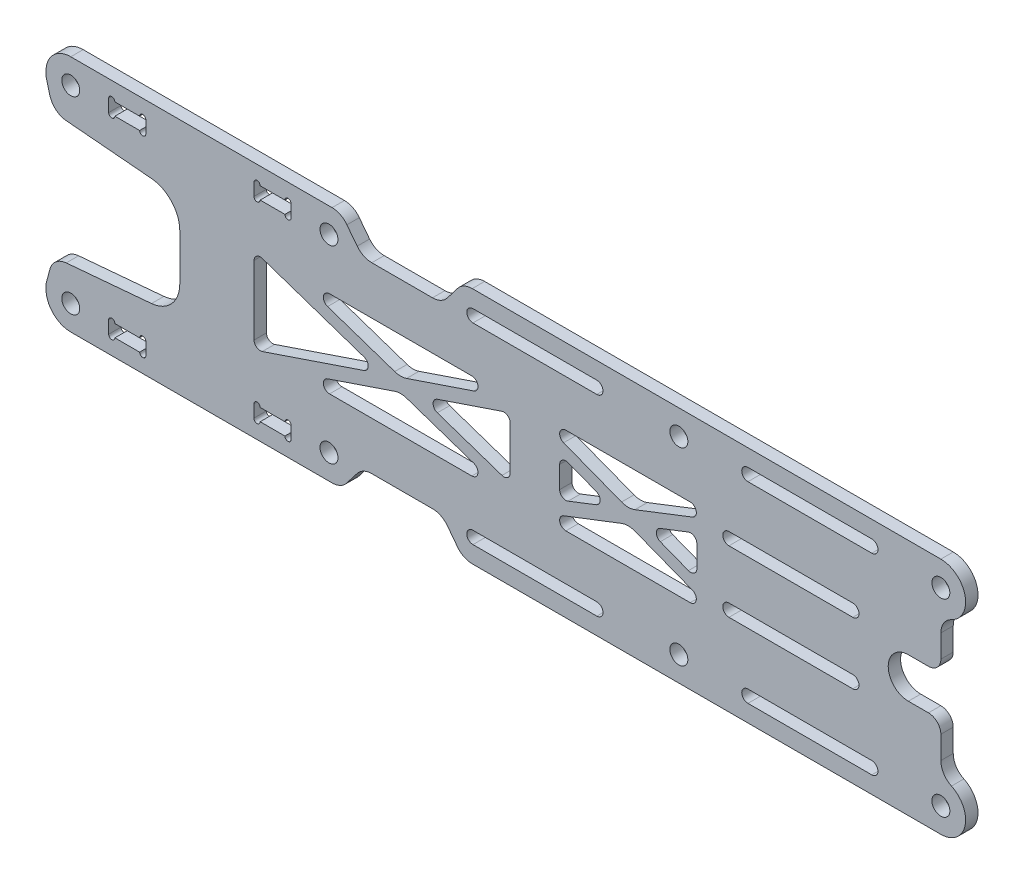
SolidWorks part; units mm, degrees
material "Thornel Mat VMA"
ref_plane "Front Plane" through (0, 0, 0) normal (0, 0, 1) x (1, 0, 0)
ref_plane "Top Plane" through (0, 0, 0) normal (0, 1, 0) x (1, 0, 0)
ref_plane "Right Plane" through (0, 0, 0) normal (1, 0, 0) x (0, 0, -1)
sketch "Sketch1" plane through (0, 0, 0) normal (0, 0, 1) x (1, 0, 0)
  line L0 (38.4052, -16.5) -> (58.4052, -16.5)
  line L1 (58.4052, -14.5) -> (38.4052, -14.5)
  line L2 (-6, -16.5) -> (14, -16.5)
  line L3 (14, -14.5) -> (-6, -14.5)
  line L4 (-59.8318, -16.5) -> (-63.8318, -16.5)
  line L5 (-64.8318, -16.5) -> (-64.8318, -14.5)
  line L6 (-63.8318, -14.5) -> (-59.8318, -14.5)
  line L7 (-58.8318, -14.5) -> (-58.8318, -16.5)
  line L8 (-6, 16.5) -> (14, 16.5)
  line L9 (14, 14.5) -> (-6, 14.5)
  line L10 (-59.8318, 16.5) -> (-63.8318, 16.5)
  line L11 (-64.8318, 16.5) -> (-64.8318, 14.5)
  line L12 (-63.8318, 14.5) -> (-59.8318, 14.5)
  line L13 (-58.8318, 14.5) -> (-58.8318, 16.5)
  line L14 (-36.3681, -16.5) -> (-40.3681, -16.5)
  line L15 (-41.3681, -16.5) -> (-41.3681, -14.5)
  line L16 (-40.3681, -14.5) -> (-36.3681, -14.5)
  line L17 (-35.3681, -14.5) -> (-35.3681, -16.5)
  line L18 (-36.3681, 16.5) -> (-40.3681, 16.5)
  line L19 (-41.3681, 16.5) -> (-41.3681, 14.5)
  line L20 (-40.3681, 14.5) -> (-36.3681, 14.5)
  line L21 (-35.3681, 14.5) -> (-35.3681, 16.5)
  line L22 (38.4052, 16.5) -> (58.4052, 16.5)
  line L23 (58.4052, 14.5) -> (38.4052, 14.5)
  line L24 (-70.9498, 19.25) -> (-28.7512, 19.25)
  line L25 (-22.3376, 14.75) -> (-12.5266, 14.75)
  line L26 (-6.113, 19.25) -> (69.5603, 19.25)
  line L27 (69.5603, 8.9254) -> (69.5603, 5.25)
  line L28 (67.5603, 3.25) -> (64.3092, 3.25)
  line L29 (64.3092, -3.25) -> (67.5603, -3.25)
  line L30 (69.5603, -5.25) -> (69.5603, -8.9254)
  line L31 (69.5603, -19.25) -> (-6.113, -19.25)
  line L32 (-28.7512, -19.25) -> (-70.9498, -19.25)
  line L33 (-74.9498, -15.25) -> (-74.9498, -14.5)
  line L34 (-74.9498, -14.5) -> (-74.3225, -12.1587)
  line L35 (-71.6862, -9.9466) -> (-57.9122, -8.7415)
  line L36 (-53.348, -3.7605) -> (-53.348, 3.7605)
  line L37 (-57.9122, 8.7415) -> (-71.6862, 9.9466)
  line L38 (-74.3225, 12.1587) -> (-74.9498, 14.5)
  line L39 (-74.9498, 14.5) -> (-74.9498, 15.25)
  line L40 (-41.348, 5.5656) -> (-41.348, -5.5656)
  line L41 (-40.0273, -6.5128) -> (-23.5895, -0.9472)
  line L42 (-23.5895, 0.9472) -> (-40.0273, 6.5128)
  line L43 (-29.1583, -7) -> (-6.1897, -7)
  line L44 (-5.869, -5.0528) -> (-16.7119, -1.3815)
  line L45 (-18.6361, -1.3815) -> (-29.479, -5.0528)
  line L46 (-29.479, 5.0528) -> (-18.6361, 1.3815)
  line L47 (-16.7119, 1.3815) -> (-5.869, 5.0528)
  line L48 (-6.1897, 7) -> (-29.1583, 7)
  line L49 (-11.7584, -0.9472) -> (-1.3207, -4.4813)
  line L50 (0, -3.5341) -> (0, 3.5341)
  line L51 (-1.3207, 4.4813) -> (-11.7584, 0.9472)
  line L52 (8.6403, 5.0669) -> (18.0001, 1.4587)
  line L53 (20.1668, 1.462) -> (29.4369, 5.068)
  line L54 (29.0744, 7) -> (9, 7)
  line L55 (-22.3376, -14.75) -> (-12.5266, -14.75)
  line L56 (8.6403, -5.1469) -> (18.0001, -1.5386)
  line L57 (20.1668, -1.5419) -> (29.4369, -5.148)
  line L58 (29.0744, -7.0799) -> (9, -7.0799)
  line L59 (8, 1.7131) -> (8, -1.8089)
  line L60 (9.3625, -2.7409) -> (13.9099, -0.9719)
  line L61 (13.9071, 0.8931) -> (9.3597, 2.6461)
  line L62 (30.1584, 1.7131) -> (30.1584, -1.8089)
  line L63 (28.7959, -2.7409) -> (24.2485, -0.9719)
  line L64 (24.2513, 0.8931) -> (28.7987, 2.6461)
  line L65 (35.3391, 6) -> (55.3391, 6)
  line L66 (55.3391, 4) -> (35.3391, 4)
  line L67 (35.3391, -6) -> (55.3391, -6)
  line L68 (55.3391, -4) -> (35.3391, -4)
  arc A6 (-26.351, 18.0497) -> (-28.7512, 19.25) centre (-28.7512, 16.25) ccw
  arc A7 (-26.351, 18.0497) -> (-24.6948, 15.8942) centre (65.9638, 87.2689) ccw
  arc A8 (-24.6948, 15.8942) -> (-22.3376, 14.75) centre (-22.3376, 17.75) ccw
  arc A9 (71.2746, 11.636) -> (69.5603, 19.25) centre (69.5603, 15.25) ccw
  arc A10 (71.2746, 11.636) -> (69.5603, 8.9254) centre (72.5603, 8.9254) ccw
  arc A11 (67.5603, 3.25) -> (69.5603, 5.25) centre (67.5603, 5.25) ccw
  arc A12 (64.3092, 3.25) -> (64.3092, -3.25) centre (64.3092, 0) ccw
  arc A13 (69.5603, -5.25) -> (67.5603, -3.25) centre (67.5603, -5.25) ccw
  arc A14 (69.5603, -8.9254) -> (71.2746, -11.636) centre (72.5603, -8.9254) ccw
  arc A15 (69.5603, -19.25) -> (71.2746, -11.636) centre (69.5603, -15.25) ccw
  arc A16 (-74.9498, -15.25) -> (-70.9498, -19.25) centre (-70.9498, -15.25) ccw
  arc A17 (-71.6862, -9.9466) -> (-74.3225, -12.1587) centre (-71.4247, -12.9352) ccw
  arc A18 (-57.9122, -8.7415) -> (-53.348, -3.7605) centre (-58.348, -3.7605) ccw
  arc A19 (-53.348, 3.7605) -> (-57.9122, 8.7415) centre (-58.348, 3.7605) ccw
  arc A20 (-74.3225, 12.1587) -> (-71.6862, 9.9466) centre (-71.4247, 12.9352) ccw
  arc A21 (-70.9498, 19.25) -> (-74.9498, 15.25) centre (-70.9498, 15.25) ccw
  arc A23 (-10.1695, 15.8942) -> (-8.5132, 18.0497) centre (-100.828, 87.2689) ccw
  arc A24 (-12.5266, 14.75) -> (-10.1695, 15.8942) centre (-12.5266, 17.75) ccw
  arc A25 (-6.113, 19.25) -> (-8.5132, 18.0497) centre (-6.113, 16.25) ccw
  arc A27 (-28.7512, -19.25) -> (-26.351, -18.0497) centre (-28.7512, -16.25) ccw
  arc A28 (-24.6948, -15.8942) -> (-26.351, -18.0497) centre (65.9638, -87.2689) ccw
  arc A29 (-22.3376, -14.75) -> (-24.6948, -15.8942) centre (-22.3376, -17.75) ccw
  arc A30 (-8.5132, -18.0497) -> (-10.1695, -15.8942) centre (-100.828, -87.2689) ccw
  arc A31 (-10.1695, -15.8942) -> (-12.5266, -14.75) centre (-12.5266, -17.75) ccw
  arc A32 (-8.5132, -18.0497) -> (-6.113, -19.25) centre (-6.113, -16.25) ccw
  arc A33 (38.4052, -14.5) -> (38.4052, -16.5) centre (38.4052, -15.5) ccw
  arc A34 (58.4052, -16.5) -> (58.4052, -14.5) centre (58.4052, -15.5) ccw
  arc A35 (-6, -14.5) -> (-6, -16.5) centre (-6, -15.5) ccw
  arc A36 (14, -16.5) -> (14, -14.5) centre (14, -15.5) ccw
  arc A37 (-59.8318, -16.5) -> (-58.8318, -16.5) centre (-59.3318, -16.5) ccw
  arc A38 (-64.8318, -16.5) -> (-63.8318, -16.5) centre (-64.3318, -16.5) ccw
  arc A39 (-63.8318, -14.5) -> (-64.8318, -14.5) centre (-64.3318, -14.5) ccw
  arc A40 (-58.8318, -14.5) -> (-59.8318, -14.5) centre (-59.3318, -14.5) ccw
  arc A41 (-6, 16.5) -> (-6, 14.5) centre (-6, 15.5) ccw
  arc A42 (14, 14.5) -> (14, 16.5) centre (14, 15.5) ccw
  arc A43 (-58.8318, 16.5) -> (-59.8318, 16.5) centre (-59.3318, 16.5) ccw
  arc A44 (-63.8318, 16.5) -> (-64.8318, 16.5) centre (-64.3318, 16.5) ccw
  arc A45 (-64.8318, 14.5) -> (-63.8318, 14.5) centre (-64.3318, 14.5) ccw
  arc A46 (-59.8318, 14.5) -> (-58.8318, 14.5) centre (-59.3318, 14.5) ccw
  arc A47 (-36.3681, -16.5) -> (-35.3681, -16.5) centre (-35.8681, -16.5) ccw
  arc A48 (-41.3681, -16.5) -> (-40.3681, -16.5) centre (-40.8681, -16.5) ccw
  arc A49 (-40.3681, -14.5) -> (-41.3681, -14.5) centre (-40.8681, -14.5) ccw
  arc A50 (-35.3681, -14.5) -> (-36.3681, -14.5) centre (-35.8681, -14.5) ccw
  arc A51 (-35.3681, 16.5) -> (-36.3681, 16.5) centre (-35.8681, 16.5) ccw
  arc A52 (-40.3681, 16.5) -> (-41.3681, 16.5) centre (-40.8681, 16.5) ccw
  arc A53 (-41.3681, 14.5) -> (-40.3681, 14.5) centre (-40.8681, 14.5) ccw
  arc A54 (-36.3681, 14.5) -> (-35.3681, 14.5) centre (-35.8681, 14.5) ccw
  arc A55 (38.4052, 16.5) -> (38.4052, 14.5) centre (38.4052, 15.5) ccw
  arc A56 (58.4052, 14.5) -> (58.4052, 16.5) centre (58.4052, 15.5) ccw
  arc A57 (-41.348, -5.5656) -> (-40.0273, -6.5128) centre (-40.348, -5.5656) ccw
  arc A58 (-23.5895, -0.9472) -> (-23.5895, 0.9472) centre (-23.9102, 0) ccw
  arc A59 (-40.0273, 6.5128) -> (-41.348, 5.5656) centre (-40.348, 5.5656) ccw
  arc A60 (-6.1897, -7) -> (-5.869, -5.0528) centre (-6.1897, -6) ccw
  arc A61 (-16.7119, -1.3815) -> (-18.6361, -1.3815) centre (-17.674, -4.2231) ccw
  arc A62 (-29.479, -5.0528) -> (-29.1583, -7) centre (-29.1583, -6) ccw
  arc A63 (-18.6361, 1.3815) -> (-16.7119, 1.3815) centre (-17.674, 4.2231) ccw
  arc A64 (-5.869, 5.0528) -> (-6.1897, 7) centre (-6.1897, 6) ccw
  arc A65 (-29.1583, 7) -> (-29.479, 5.0528) centre (-29.1583, 6) ccw
  arc A66 (-1.3207, -4.4813) -> (0, -3.5341) centre (-1, -3.5341) ccw
  arc A67 (0, 3.5341) -> (-1.3207, 4.4813) centre (-1, 3.5341) ccw
  arc A68 (-11.7584, 0.9472) -> (-11.7584, -0.9472) centre (-11.4377, 0) ccw
  arc A69 (9, 7) -> (8.6403, 5.0669) centre (9, 6) ccw
  arc A70 (18.0001, 1.4587) -> (20.1668, 1.462) centre (19.0792, 4.2579) ccw
  arc A71 (29.4369, 5.068) -> (29.0744, 7) centre (29.0744, 6) ccw
  arc A72 (8.6403, -5.1469) -> (9, -7.0799) centre (9, -6.0799) ccw
  arc A73 (20.1668, -1.5419) -> (18.0001, -1.5386) centre (19.0792, -4.3378) ccw
  arc A74 (29.0744, -7.0799) -> (29.4369, -5.148) centre (29.0744, -6.0799) ccw
  arc A75 (8, -1.8089) -> (9.3625, -2.7409) centre (9, -1.8089) ccw
  arc A76 (13.9099, -0.9719) -> (13.9071, 0.8931) centre (13.5474, -0.04) ccw
  arc A77 (9.3597, 2.6461) -> (8, 1.7131) centre (9, 1.7131) ccw
  arc A78 (28.7959, -2.7409) -> (30.1584, -1.8089) centre (29.1584, -1.8089) ccw
  arc A79 (24.2513, 0.8931) -> (24.2485, -0.9719) centre (24.611, -0.04) ccw
  arc A80 (30.1584, 1.7131) -> (28.7987, 2.6461) centre (29.1584, 1.7131) ccw
  arc A81 (35.3391, 6) -> (35.3391, 4) centre (35.3391, 5) ccw
  arc A82 (55.3391, 4) -> (55.3391, 6) centre (55.3391, 5) ccw
  arc A83 (35.3391, -4) -> (35.3391, -6) centre (35.3391, -5) ccw
  arc A84 (55.3391, -6) -> (55.3391, -4) centre (55.3391, -5) ccw
extrude "Boss-Extrude1" add sketch "Sketch1" along normal blind 2
hole_wizard "M2.5 Clearance Hole1" positions "Sketch2" profile "Sketch3" hole size "M2.5" standard "ANSI Metric" end condition up to next
sketch "Sketch2" plane through (0, 0, 2) normal (0, 0, 1) x (1, 0, 0)
  line L4 (-70.9498, 15.25) -> (69.5603, 15.25) construction
  line L6 (-29.25, 15.25) -> (-29.25, -15.25) construction
  line L8 (27.25, -15.25) -> (27.25, 15.25) construction
  line L11 (-70.9498, -15.25) -> (69.5603, -15.25) construction
  point P0 (-70.9498, 15.25)
  point P3 (-70.9498, -15.25)
  point P6 (-29.25, -15.25)
  point P9 (-29.25, 15.25)
  point P12 (27.25, 15.25)
  point P15 (27.25, -15.25)
  point P18 (69.5603, -15.25)
  point P21 (69.5603, 15.25)
  dimension "D1" = 41.6998
  dimension "D2" = 56.5
sketch "Sketch3" plane through (-70.9498, 15.25, 2) normal (1, 0, 0) x (0, -1, 0)
  line L0 (0, 0) -> (0, 2)
  line L1 (0, 2) -> (1.45, 2)
  line L2 (1.45, 2) -> (1.45, 0)
  line L5 (1.45, 0) -> (0, 0)
  line L11 (0, -6.35) -> (0, 107.95) construction
  dimension "Thru Hole Dia." = 2.9
  dimension "Thru Hole Depth" = 2
